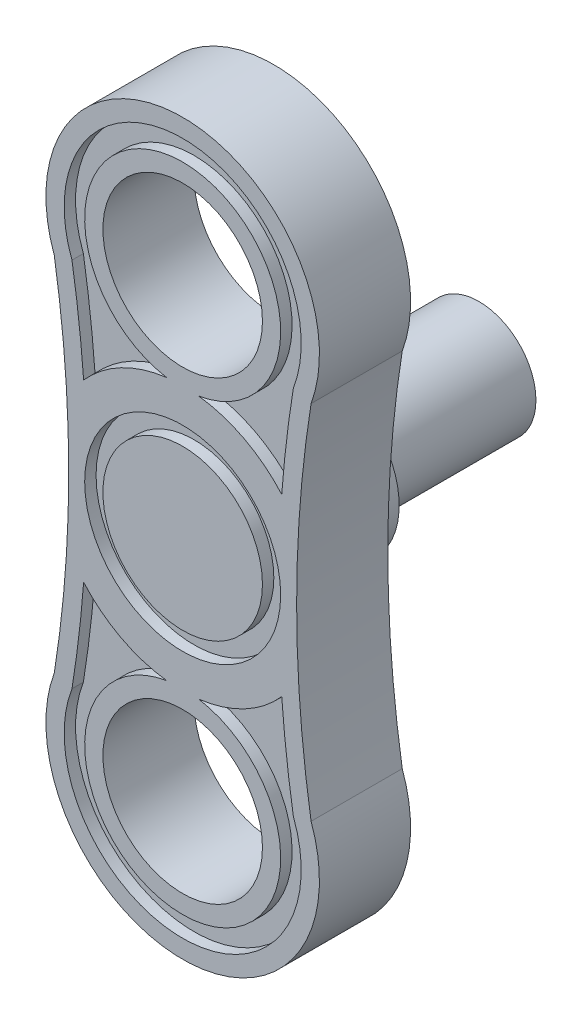
SolidWorks part; units mm, degrees
material "1060 Alloy"
ref_plane "Front Plane" through (0, 0, 0) normal (0, 0, 1) x (1, 0, 0)
ref_plane "Top Plane" through (0, 0, 0) normal (0, 1, 0) x (1, 0, 0)
ref_plane "Right Plane" through (0, 0, 0) normal (1, 0, 0) x (0, 0, -1)
sketch "Sketch1" plane through (0, 0, 0) normal (0, 0, 1) x (1, 0, 0)
  line L0 (0, -55) -> (0, 55) construction
  arc A0 (56.3382, -20.64) -> (-56.3382, -20.64) centre (0, 0) ccw
  arc A1 (-56.3382, -179.36) -> (56.3382, -179.36) centre (0, -200) ccw
  arc A2 (-56.3382, -179.36) -> (-56.3382, -20.64) centre (-550, -100) ccw
  arc A3 (56.3382, -179.36) -> (56.3382, -20.64) centre (550, -100) cw
extrude "Boss-Extrude1" add sketch "Sketch1" against normal blind 40
sketch "Sketch2" plane through (0, 0, 0) normal (0, 0, 1) x (1, 0, 0)
  line L1 (0, -55) -> (0, 55) construction
  line L2 (-43, -100) -> (43, -100) construction
  circle A0 centre (0, 0) radius 35
  arc A1 (7.0085, -42.425) -> (-7.0085, -42.425) centre (0, 0) ccw
  circle A3 centre (0, -100) radius 35
  circle A4 centre (0, -100) radius 43
  arc A5 (7.0085, -157.575) -> (43.4545, -138.4149) centre (0, -100) ccw
  circle A7 centre (0, -200) radius 35
  arc A8 (7.0085, -157.575) -> (-7.0085, -157.575) centre (0, -200) cw
  arc A19 (-43.4545, -138.4149) -> (-7.0085, -157.575) centre (0, -100) ccw
  arc A20 (43.4545, -61.5851) -> (7.0085, -42.425) centre (0, -100) ccw
  arc A21 (43.4545, -138.4149) -> (48.5672, -181.4198) centre (550, -100) ccw
  arc A22 (-42.0773, -108.8602) -> (-42.0773, -91.1398) centre (-550, -100) ccw
  arc A23 (-48.5672, -181.4198) -> (48.5672, -181.4198) centre (0, -200) ccw
  arc A24 (48.5672, -18.5802) -> (48.5672, -181.4198) centre (550, -100) ccw
  arc A25 (48.5672, -18.5802) -> (-48.5672, -18.5802) centre (0, 0) ccw
  arc A26 (-48.5672, -181.4198) -> (-48.5672, -18.5802) centre (-550, -100) ccw
  arc A27 (-48.5672, -181.4198) -> (48.5672, -181.4198) centre (0, -200) ccw
  arc A28 (48.5672, -18.5802) -> (43.4545, -61.5851) centre (550, -100) ccw
  arc A29 (48.5672, -18.5802) -> (-48.5672, -18.5802) centre (0, 0) ccw
  arc A30 (-48.5672, -181.4198) -> (-43.4545, -138.4149) centre (-550, -100) ccw
  arc A31 (-43.4545, -61.5851) -> (-48.5672, -18.5802) centre (-550, -100) ccw
  arc A32 (42.0773, -91.1398) -> (42.0773, -108.8602) centre (550, -100) ccw
  arc A33 (-7.0085, -42.425) -> (-43.4545, -61.5851) centre (0, -100) ccw
  dimension "D2" = 86
  dimension "D3" = 70
  dimension "D6" = 116
  dimension "D7" = 86
  dimension "D8" = 70
  dimension "D9" = 100
  dimension "D4" = 8
extrude "Cut-Extrude1" cut sketch "Sketch2" against normal blind 5 contours A21 A27 A30 A19 A8 A5 | A3 | A4 | A33 A31 A29 A28 A20 A1
extrude "Cut-Extrude2" cut sketch "Sketch2<5>" against normal through all and the other way through all contours A0 | A7
sketch "Sketch2<5>" plane through (0, 0, 0) normal (0, 0, 1) x (1, 0, 0) same geometry as "Sketch2"
sketch "Sketch4" plane through (0, 0, -40) normal (0, 0, -1) x (-1, 0, 0)
  circle A0 centre (0, -100) radius 25
  circle A1 centre (0, -100) radius 35
  dimension "D1" = 70
  dimension "D2" = 50
extrude "Boss-Extrude3" add sketch "Sketch4" along normal blind 20 contours A1
extrude "Boss-Extrude4" add sketch "Sketch4<4>" along normal blind 90 contours A0
sketch "Sketch4<4>" plane through (0, 0, -40) normal (0, 0, -1) x (-1, 0, 0) same geometry as "Sketch4"
